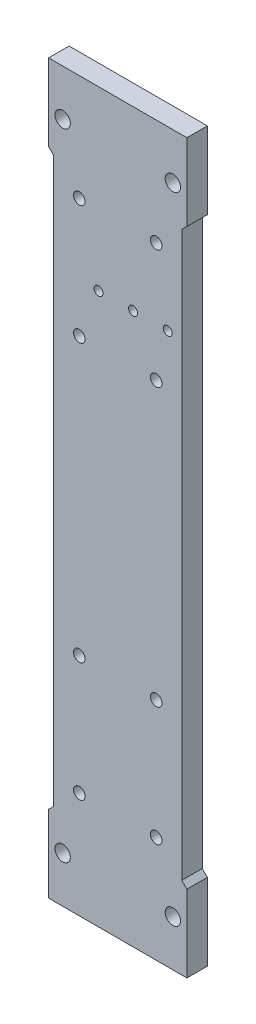
SolidWorks part; units mm, degrees
ref_plane "Front" through (0, 0, 0) normal (0, 0, 1) x (1, 0, 0)
ref_plane "Top" through (0, 0, 0) normal (0, 1, 0) x (1, 0, 0)
ref_plane "Right" through (0, 0, 0) normal (1, 0, 0) x (0, 0, -1)
sketch "Esquisse1" plane through (0, 0, 0) normal (0, 0, 1) x (1, 0, 0)
  line L1 (0, 0) -> (50, 0)
  line L2 (0, 0) -> (0, 284)
  line L3 (0, 284) -> (50, 284)
  line L4 (50, 0) -> (50, 284)
  dimension "D1" = 50
  dimension "D2" = 284
extrude "Boss.-Extru.1" add sketch "Esquisse1" along normal blind 8
sketch "Esquisse2" plane through (0, 0, 8) normal (0, 0, 1) x (1, 0, 0)
  line L0 (25, 284) -> (25, 0) construction
  line L1 (50, 284) -> (0, 284) construction
  line L2 (0, 0) -> (50, 0) construction
  line L3 (25, 142) -> (0, 142) construction
  line L4 (0, 284) -> (0, 0) construction
  circle A0 centre (3.5, 18) radius 3
  circle A1 centre (46.5, 18) radius 3
  circle A2 centre (46.5, 266) radius 3
  circle A3 centre (3.5, 266) radius 3
  dimension "D2" = 43
  dimension "D3" = 6
  dimension "D1" = 248
extrude "Enlèv. mat.-Extru.1" cut sketch "Esquisse2" against normal through all
sketch "Esquisse3" plane through (0, 0, 8) normal (0, 0, 1) x (1, 0, 0)
  line L0 (25, 284) -> (25, 0) construction
  line L1 (50, 284) -> (0, 284) construction
  line L2 (0, 0) -> (50, 0) construction
  line L3 (0, 0) -> (0, 30)
  line L4 (0, 284) -> (0, 0) construction
  line L5 (0, 30) -> (-2, 30)
  line L6 (-2, 30) -> (-2, 0)
  line L7 (-2, 0) -> (0, 0)
  line L8 (52, 0) -> (50, 0)
  line L9 (52, 30) -> (52, 0)
  line L10 (50, 30) -> (52, 30)
  line L11 (50, 0) -> (50, 30)
  line L12 (25, 142) -> (0, 142) construction
  line L13 (50, 284) -> (50, 254)
  line L14 (50, 254) -> (52, 254)
  line L15 (52, 254) -> (52, 284)
  line L16 (52, 284) -> (50, 284)
  line L17 (-2, 284) -> (0, 284)
  line L18 (-2, 254) -> (-2, 284)
  line L19 (0, 254) -> (-2, 254)
  line L20 (0, 284) -> (0, 254)
  dimension "D1" = 2
  dimension "D2" = 30
extrude "Boss.-Extru.2" add sketch "Esquisse3" against normal up to vertex (8 mm away) up to point (50, 284, 0)
chamfer "Chanfrein1" distance 2 angle 45 4 edges at (50, 30, 4) (0, 30, 4) (0, 254, 4) (50, 254, 4)
sketch "Esquisse4" plane through (0, 0, 8) normal (0, 0, 1) x (1, 0, 0)
  line L0 (0, 142) -> (50, 142) construction
  line L1 (0, 252) -> (0, 32) construction
  line L2 (50, 32) -> (50, 252) construction
  line L3 (0, 88) -> (50, 88) construction
  line L4 (0, 41.5) -> (50, 41.5) construction
  line L5 (25, 142) -> (25, 41.5) construction
  line L6 (10, 88) -> (10, 41.5) construction
  line L7 (40, 88) -> (40, 41.5) construction
  line L8 (40, 196) -> (40, 242.5) construction
  line L9 (10, 196) -> (10, 242.5) construction
  circle A0 centre (10, 41.5) radius 2.25
  circle A1 centre (10, 88) radius 2.25
  circle A2 centre (40, 88) radius 2.25
  circle A3 centre (40, 41.5) radius 2.25
  circle A4 centre (40, 242.5) radius 2.25
  circle A5 centre (40, 196) radius 2.25
  circle A6 centre (10, 196) radius 2.25
  circle A7 centre (10, 242.5) radius 2.25
  dimension "D1" = 4.5
  dimension "D2" = 30
  dimension "D3" = 100.5
  dimension "D4" = 54
extrude "Enlèv. mat.-Extru.2" cut sketch "Esquisse4" against normal through all
sketch "Esquisse5" plane through (0, 0, 8) normal (0, 0, 1) x (1, 0, 0)
  line L0 (0, 215) -> (50, 215) construction
  line L1 (0, 252) -> (0, 32) construction
  line L2 (50, 32) -> (50, 252) construction
  line L3 (31, 215) -> (31, 233.6393) construction
  line L4 (52, 284) -> (-2, 284) construction
  circle A0 centre (44.5, 215) radius 1.75
  circle A1 centre (31, 215) radius 1.75
  circle A2 centre (17.5, 215) radius 1.75
  dimension "D1" = 13.5
  dimension "D2" = 3.5
  dimension "D3" = 69
  dimension "D4" = 5.5
extrude "Enlèv. mat.-Extru.3" cut sketch "Esquisse5" against normal through all
